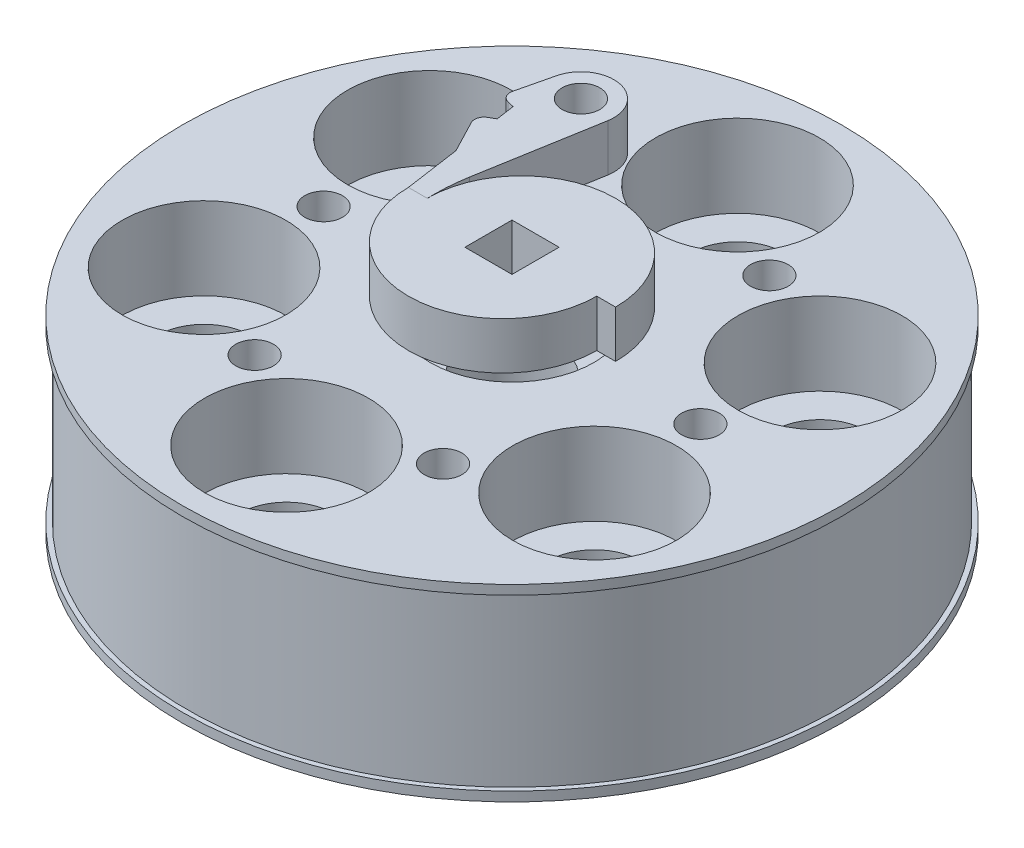
SolidWorks part; units mm, degrees
ref_plane "Front Plane" through (0, 0, 0) normal (0, 0, 1) x (1, 0, 0)
ref_plane "Top Plane" through (0, 0, 0) normal (0, 1, 0) x (1, 0, 0)
ref_plane "Right Plane" through (0, 0, 0) normal (1, 0, 0) x (0, 0, -1)
sketch "Sketch1" plane through (0, 0, 0) normal (0, 1, 0) x (1, 0, 0)
  circle A0 centre (0, 0) radius 44.45
  dimension "D1" = 88.9
extrude "Boss-Extrude1" add sketch "Sketch1" along normal mid plane 25.4
sketch "Sketch2" plane through (0, 12.7, 0) normal (0, 1, 0) x (1, 0, 0)
  line L0 (0, 0) -> (0, 44.45) construction
  circle A0 centre (0, 0) radius 44.45 construction
  circle A1 centre (0, 30.3967) radius 11.05
  circle A2 centre (26.3243, 15.1983) radius 11.05
  circle A3 centre (26.3243, -15.1983) radius 11.05
  circle A4 centre (0, -30.3967) radius 11.05
  circle A5 centre (-26.3243, -15.1983) radius 11.05
  circle A6 centre (-26.3243, 15.1983) radius 11.05
  circle A7 centre (0, 0) radius 6.8494
  dimension "D1" = 22.1
  dimension "D2" = 6
extrude "Cut-Extrude1" cut sketch "Sketch2" against normal blind 25.4 contours A1 | A6 | A4 | A2 | A3 | A5
sketch "Sketch3" plane through (0, 0, 0) normal (0, 1, 0) x (1, 0, 0)
  line L0 (0, 0) -> (0, 30.3967) construction
  line L1 (0, 0) -> (26.3243, 15.1983) construction
  circle A0 centre (-26.3243, -15.1983) radius 11.05 construction
  circle A1 centre (0, -30.3967) radius 11.05 construction
  circle A2 centre (26.3243, -15.1983) radius 11.05 construction
  circle A3 centre (26.3243, 15.1983) radius 11.05 construction
  circle A4 centre (0, 30.3967) radius 11.05 construction
  circle A5 centre (-26.3243, 15.1983) radius 11.05 construction
  circle A6 centre (-26.3243, -15.1983) radius 11.05
  circle A7 centre (0, -30.3967) radius 11.05
  circle A8 centre (26.3243, -15.1983) radius 11.05
  circle A9 centre (26.3243, 15.1983) radius 11.05
  circle A10 centre (0, 30.3967) radius 11.05
  circle A11 centre (-26.3243, 15.1983) radius 11.05
  circle A12 centre (0, 30.3967) radius 6.35
  circle A13 centre (26.3243, 15.1983) radius 6.35
  circle A14 centre (26.3243, -15.1983) radius 6.35
  circle A15 centre (0, -30.3967) radius 6.35
  circle A16 centre (-26.3243, -15.1983) radius 6.35
  circle A17 centre (-26.3243, 15.1983) radius 6.35
  dimension "D1" = 12.7
  dimension "D3" = 60
  dimension "D2" = 6
extrude "Boss-Extrude2" add sketch "Sketch3" along normal mid plane 3.175
sketch "Sketch4" plane through (0, 12.7, 0) normal (0, 1, 0) x (1, 0, 0)
  circle A0 centre (0, 0) radius 11.05
  circle A1 centre (0, 0) radius 6.35
  dimension "D1" = 22.1
  dimension "D2" = 12.7
extrude "Cut-Extrude2" cut sketch "Sketch4" against normal blind 7
extrude "Cut-Extrude3" cut sketch "Sketch4<2>" against normal blind 30.622 contours A1 region at (0, 12.7, 0)
sketch "Sketch4<2>" plane through (0, 12.7, 0) normal (0, 1, 0) x (1, 0, 0) same geometry as "Sketch4"
mirror "Mirror1" about plane through (0, 0, 0) normal (0, 1, 0) of "Cut-Extrude2"
ref_plane "Plane1" through (0, 14.2875, 0) normal (0, 1, 0) x (1, 0, 0)
sketch "Sketch7" plane through (0, 14.2875, 0) normal (0, 1, 0) x (1, 0, 0)
  line L0 (-13.97, 0) -> (-11.43, 0)
  line L1 (11.43, 0) -> (13.97, 0)
  line L2 (11.43, 0) -> (-11.43, 0) construction
  line L4 (-3.175, 3.175) -> (3.175, 3.175)
  line L5 (-3.175, 3.175) -> (-3.175, -3.175)
  line L6 (-3.175, -3.175) -> (3.175, -3.175)
  line L7 (3.175, 3.175) -> (3.175, -3.175)
  line L8 (-3.175, 3.175) -> (3.175, -3.175) construction
  line L9 (-3.175, -3.175) -> (3.175, 3.175) construction
  arc A0 (13.97, 0) -> (-11.43, 0) centre (1.27, 0) ccw
  arc A1 (-13.97, 0) -> (11.43, 0) centre (-1.27, 0) ccw
  point P3 (0, 0)
  point P4 (0, 0)
  point P5 (0, 0)
  dimension "D1" = 12.7
  dimension "D2" = 12.7
  dimension "D3" = 27.94
  dimension "D4" = 6.35
  dimension "D5" = 6.35
extrude "Boss-Extrude3" add sketch "Sketch7" along normal blind 6.35 separate body
mirror "Mirror3" about plane through (0, 0, 0) normal (0, 1, 0) of bodies 108
sketch "Sketch8" plane through (0, 20.6375, 0) normal (0, 1, 0) x (1, 0, 0)
  line L0 (-11.43, 0) -> (-11.43, 3.175)
  line L1 (0, 0) -> (-22.225, 38.4948) construction
  line L2 (-11.43, 0) -> (-13.97, 0)
  line L3 (11.43, 0) -> (13.97, 0)
  line L4 (-11.43, 0) -> (-13.97, 0)
  line L5 (11.43, 0) -> (13.97, 0) construction
  line L6 (-17.145, 21.997) -> (-13.97, 0)
  line L7 (0, 0) -> (0, 44.45) construction
  line L8 (-11.43, 3.175) -> (-8.3194, 21.2429)
  line L9 (-17.0235, 23.0293) -> (-18.1673, 18.2385)
  line L10 (-17.227, 16.7083) -> (-16.3515, 16.4992)
  line L11 (-20.1208, 14.672) -> (-12.0483, 15.8372) construction
  line L12 (-16.8132, 13.512) -> (-15.9886, 13.9853)
  line L13 (-17.3072, 11.8236) -> (-15.052, 7.4963)
  circle A0 centre (0, 0) radius 44.45 construction
  arc A1 (-8.3194, 21.2429) -> (-16.9636, 20.7401) centre (-12.7, 21.997) ccw
  arc A2 (13.97, 0) -> (-11.43, 0) centre (1.27, 0) ccw
  arc A3 (-13.97, 0) -> (11.43, 0) centre (-1.27, 0) ccw
  arc A4 (13.97, 0) -> (-11.43, 0) centre (1.27, 0) ccw construction
  arc A5 (-13.97, 0) -> (11.43, 0) centre (-1.27, 0) ccw construction
  circle A6 centre (-12.7, 21.997) radius 2.54
  arc A7 (-18.1673, 18.2385) -> (-17.227, 16.7083) centre (-16.9321, 17.9435) ccw
  arc A8 (-16.8132, 13.512) -> (-17.3072, 11.8236) centre (-16.181, 12.4105) ccw
  point P29 (-18.4623, 17.0032)
  point P32 (-17.8708, 12.9049)
  line M10 (-11.43, 0) -> (-13.97, 0)
  dimension "D3" = 8.89
  dimension "D6" = 5.08
  dimension "D8" = 1.27
  dimension "D2" = 30
  dimension "D4" = 25.4
  dimension "D5" = 3.175
  dimension "D7" = 1.27
  dimension "D1" = 0
extrude "Boss-Extrude4" add sketch "Sketch8" against normal blind 6.35 separate body contours L8 A1 L6 L0 A6 M10 | L12 A8 L13 L6 | L9 A7 L10 L6 A1 | L6 A1 region at (-12.7736, 20.6375, -14.3983) region at (-16.2435, 20.6375, -11.3953) region at (-17.2875, 20.6375, -18.6917) region at (-17.0723, 20.6375, -21.366)
fillet "Fillet1" radius 25.4 1 edges at (-11.43, 17.4625, -3.175)
sketch "Sketch9" plane through (0, 12.7, 0) normal (0, 1, 0) x (1, 0, 0)
  circle A0 centre (-12.7, 21.997) radius 2.54 construction
  circle A1 centre (-12.7, 21.997) radius 2.54
  circle A2 centre (12.7, 21.997) radius 2.54
  circle A3 centre (25.4, 0) radius 2.54
  circle A4 centre (12.7, -21.997) radius 2.54
  circle A5 centre (-12.7, -21.997) radius 2.54
  circle A6 centre (-25.4, 0) radius 2.54
  dimension "D1" = 6
extrude "Cut-Extrude5" cut sketch "Sketch9" against normal through all
mirror "Mirror4" about plane through (0, 0, 0) normal (0, 1, 0) of bodies 110
sketch "Sketch10" plane through (0, 0, 0) normal (1, 0, 0) x (0, 0, -1)
  line L0 (44.45, -12.7) -> (44.45, 12.7) construction
  line L1 (44.45, -12.7) -> (44.45, 12.7)
  line L2 (0, 0) -> (44.45, 0) construction
  line L3 (44.45, 12.7) -> (-44.45, 12.7) construction
  line L4 (43.815, 11.43) -> (44.45, 11.43)
  line L5 (43.815, 11.43) -> (43.815, -11.43)
  line L6 (43.815, -11.43) -> (44.45, -11.43)
  line L7 (44.45, 11.43) -> (44.45, -11.43)
  line L8 (43.815, 11.43) -> (44.45, -11.43) construction
  line L9 (43.815, -11.43) -> (44.45, 11.43) construction
  line L10 (0, 0) -> (0, 12.7) construction
  point P5 (44.1325, 0)
  dimension "D1" = 0.635
  dimension "D2" = 1.27
revolve "Cut-Revolve1" cut sketch "Sketch10" angle 360 about L10 region at (0, 0, -44.1325)
